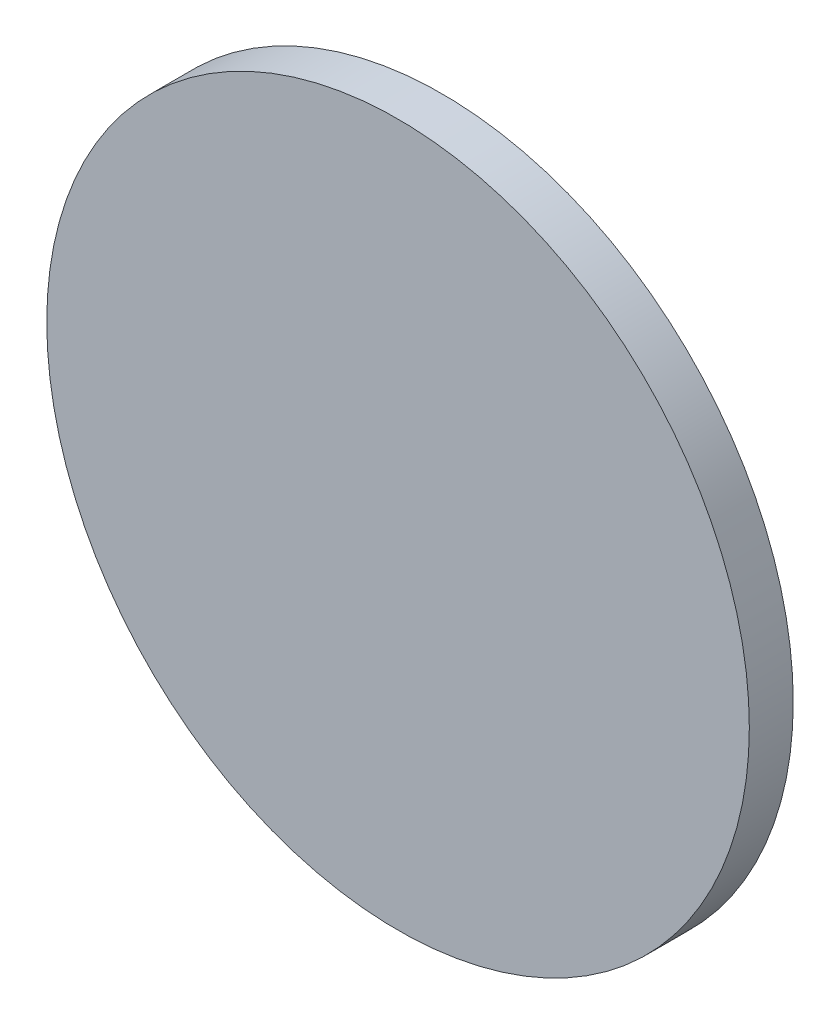
SolidWorks part; units mm, degrees
ref_plane "Front Plane" through (0, 0, 0) normal (0, 0, 1) x (1, 0, 0)
ref_plane "Top Plane" through (0, 0, 0) normal (0, 1, 0) x (1, 0, 0)
ref_plane "Right Plane" through (0, 0, 0) normal (1, 0, 0) x (0, 0, -1)
sketch "Sketch1" plane through (0, 0, 0) normal (0, 0, 1) x (1, 0, 0)
  circle A0 centre (0, 0) radius 24
  dimension "addendumDiameter " = 48
extrude "Boss-Extrude1" add sketch "Sketch1" along normal blind 3
sketch "Sketch2" plane through (0, 0, 3) normal (0, 0, 1) x (1, 0, 0)
  line L0 (0, 0) -> (0, 31.2008) construction
  line L1 (0, 0) -> (-3.262, 31.0361) construction
  circle A0 centre (0, 0) radius 20.625 construction
  circle A1 centre (0, 0) radius 21.1431 construction
  circle A2 centre (0, 0) radius 22.5 construction
  dimension "dedendumCircle" = 41.25
  dimension "baseDiameter" = 42.2862
  dimension "pitchDiameter" = 45
  dimension "D1" = 6
equation "\"module\"= 1.5"
equation "\"teeth\"= 30"
equation "\"pressureAngle\" = 20deg"
equation "\"gearThickness\" = 3"
equation "\"addendumFactor\"= 1"
equation "\"dedendumFactor\"= 1.25"
equation "\"pitch\"= 1/\"module\""
equation "\"pitchDiameter\"= \"teeth\" / \"pitch\""
equation "\"addendum\"= \"addendumFactor\" / \"pitch\""
equation "\"dedendum\"= \"dedendumFactor\" / \"pitch\""
equation "\"addendumDiameter @Sketch1\"= \"pitchDiameter\" + 2 * \"addendum\""
equation "\"D1@Boss-Extrude1\"= \"gearThickness\""
equation "\"dedendumCircle@Sketch2\" = \"pitchDiameter\" - 2 * \"dedendum\""
equation "\"baseDiameter@Sketch2\"=\"pitchDiameter\" * cos ( \"pressureAngle\" )"
equation "\"pitchDiameter@Sketch2\"=\"pitchDiameter\""
equation "\"D1@Sketch2\"=180/\"teeth\""
